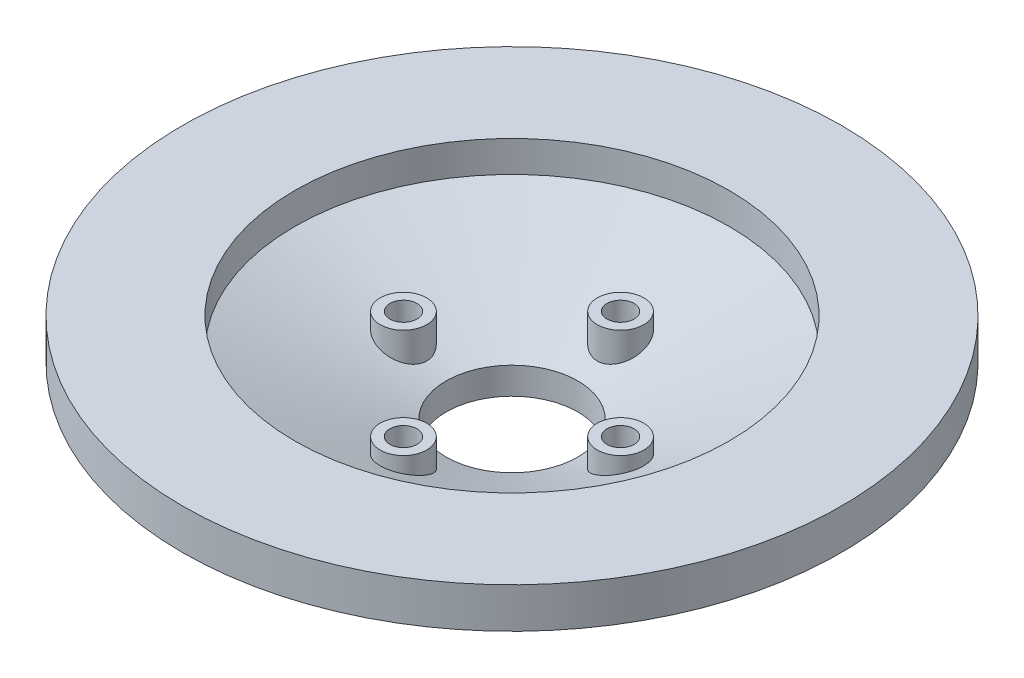
SolidWorks part; units mm, degrees
ref_plane "Front Plane" through (0, 0, 0) normal (0, 0, 1) x (1, 0, 0)
ref_plane "Top Plane" through (0, 0, 0) normal (0, 1, 0) x (1, 0, 0)
ref_plane "Right Plane" through (0, 0, 0) normal (1, 0, 0) x (0, 0, -1)
sketch "Sketch1" plane through (0, 0, 0) normal (0, 0, 1) x (1, 0, 0)
  line L0 (0, 29.2472) -> (0, -29.2472) construction
  line L1 (17, 0) -> (22, 0)
  line L2 (22, 0) -> (22, 2)
  line L3 (22, 2) -> (67.7, 19.6)
  line L4 (67.7, 19.6) -> (85, 19.6)
  line L5 (85, 19.6) -> (85, 30)
  line L6 (85, 30) -> (56, 30)
  line L7 (17, 0) -> (17, 6.9382)
  line L8 (17, 6.9382) -> (56, 21.9579)
  line L9 (56, 21.9579) -> (56, 30)
  point P3 (17, 6.9382)
  point P4 (0, 0)
  dimension "D1" = 17
  dimension "D2" = 22
  dimension "D3" = 17.3
  dimension "D4" = 10.4
  dimension "D5" = 56
  dimension "D6" = 85
  dimension "D7" = 2
  dimension "D8" = 30
revolve "Revolve1" add sketch "Sketch1" angle 360 about L0
ref_plane "Plane1" through (0, 2, 0) normal (0, -1, 0) x (-1, 0, 0)
sketch "Sketch2" plane through (0, 2, 0) normal (0, -1, 0) x (-1, 0, 0)
  arc A1 (5.9655, 27.3571) -> (-5.9655, 27.3571) centre (0, 28) ccw
  circle A2 centre (0, 28) radius 3.5
  circle A3 centre (0, 28) radius 6
  circle A4 centre (28, 0) radius 6
  circle A5 centre (28, 0) radius 3.5
  circle A6 centre (0, -28) radius 6
  circle A7 centre (0, -28) radius 3.5
  circle A8 centre (-28, 0) radius 6
  circle A9 centre (-28, 0) radius 3.5
  point P19 (0, 0)
  dimension "D2" = 12
  dimension "D3" = 7
  dimension "D4" = 4
extrude "Boss-Extrude1" add sketch "Sketch2" against normal blind 15 contours A1 A3 A2 | A6 A7 | A8 A9 | A5 | A4 region at (0, 2, -22.1697) region at (-28, 2, 0) region at (5.8303, 2, 28) region at (33.8303, 2, 0)
sketch "Sketch3" plane through (0, 2, 0) normal (0, -1, 0) x (-1, 0, 0)
  arc A0 (-27.3571, -5.9655) -> (-5.9655, -27.3571) centre (0, 0) ccw
  circle A1 centre (0, 28) radius 6
  circle A2 centre (0, -28) radius 6
  circle A3 centre (28, 0) radius 6
  circle A4 centre (0, 0) radius 6
  circle A5 centre (-28, 0) radius 6
  arc A6 (-5.9655, 27.3571) -> (-27.3571, 5.9655) centre (0, 0) ccw
  arc A7 (27.3571, 5.9655) -> (5.9655, 27.3571) centre (0, 0) ccw
  arc A8 (5.9655, -27.3571) -> (27.3571, -5.9655) centre (0, 0) ccw
extrude "Boss-Extrude2" add sketch "Sketch3" against normal up to surface contours A2 A8 A3 A7 A1 A6 A5 A0 A4 region at (22.9601, 2, 4.5259) up to face at (0, 19.6, 67.7)
sketch "Sketch4" plane through (0, 2, 0) normal (0, -1, 0) x (-1, 0, 0)
  circle A0 centre (0, 0) radius 3.5
  circle A1 centre (0, 0) radius 3.5
  circle A2 centre (0, 0) radius 3.5
  circle A3 centre (0, 28) radius 3.5
  circle A5 centre (28, 0) radius 3.5
  circle A6 centre (0, 0) radius 3.5
  circle A7 centre (0, -28) radius 3.5
  circle A8 centre (0, 0) radius 3.5
  circle A9 centre (0, 0) radius 3.5
  arc A10 (-31.4205, -0.7415) -> (-24.5795, 0.7415) centre (-28, 0) cw
  circle A11 centre (-28, 0) radius 3.5 construction
  circle A12 centre (-28, 0) radius 3.5
extrude "Cut-Extrude1" cut sketch "Sketch4" against normal through all contours A3 | A5 | A12 | A7
